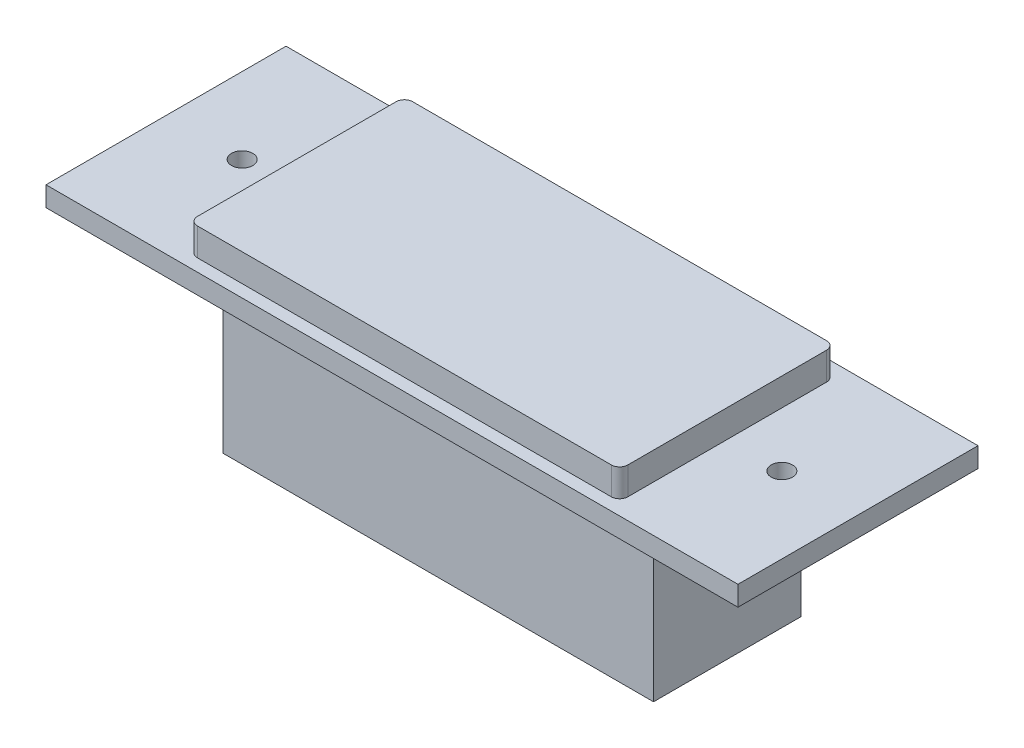
SolidWorks part; units mm, degrees
ref_plane "Front Plane" through (0, 0, 0) normal (0, 0, 1) x (1, 0, 0)
ref_plane "Top Plane" through (0, 0, 0) normal (0, 1, 0) x (1, 0, 0)
ref_plane "Right Plane" through (0, 0, 0) normal (1, 0, 0) x (0, 0, -1)
sketch "Sketch1" plane through (0, 0, 0) normal (0, 1, 0) x (1, 0, 0)
  line L1 (-33.02, 16.51) -> (33.02, 16.51)
  line L2 (-33.02, 16.51) -> (-33.02, -16.51)
  line L3 (-33.02, -16.51) -> (33.02, -16.51)
  line L4 (33.02, 16.51) -> (33.02, -16.51)
  line L5 (-33.02, 16.51) -> (33.02, -16.51) construction
  line L6 (-33.02, -16.51) -> (33.02, 16.51) construction
  point P0 (0, 0)
  dimension "D1" = 66.04
  dimension "D2" = 33.02
extrude "Boss-Extrude1" add sketch "Sketch1" along normal blind 4.2418
fillet "Fillet1" radius 1.27 4 edges at (33.02, 2.1209, 16.51) (33.02, 2.1209, -16.51) (-33.02, 2.1209, -16.51) (-33.02, 2.1209, 16.51)
sketch "Sketch2" plane through (0, 0, 0) normal (0, -1, 0) x (1, 0, 0)
  line L1 (53.086, 18.415) -> (-53.086, 18.415)
  line L2 (53.086, 18.415) -> (53.086, -18.415)
  line L3 (53.086, -18.415) -> (-53.086, -18.415)
  line L4 (-53.086, 18.415) -> (-53.086, -18.415)
  line L5 (53.086, 18.415) -> (-53.086, -18.415) construction
  line L6 (53.086, -18.415) -> (-53.086, 18.415) construction
  point P0 (0, 0)
  dimension "D1" = 36.83
  dimension "D2" = 106.172
extrude "Boss-Extrude2" add sketch "Sketch2" along normal blind 3.048
sketch "Sketch3" plane through (0, 0, 0) normal (0, 1, 0) x (1, 0, 0)
  line L0 (-53.086, 0) -> (-41.402, 0) construction
  line L1 (-53.086, -18.415) -> (-53.086, 18.415) construction
  line L2 (-41.402, 0) -> (41.402, 0) construction
  line L3 (41.402, 0) -> (53.086, 0) construction
  line L4 (53.086, 18.415) -> (53.086, -18.415) construction
  dimension "D1" = 82.804
hole_wizard "#4 Clearance Hole1" positions "Sketch4" profile "Sketch5" hole size "#4" standard "ANSI Inch" end condition through all
sketch "Sketch4" plane through (0, 0, 0) normal (0, 1, 0) x (1, 0, 0)
  point P0 (-41.402, 0)
  point P3 (41.402, 0)
sketch "Sketch5" plane through (-41.402, 0, 0) normal (1, 0, 0) x (0, 0, 1)
  line L0 (0, 0) -> (0, 3.048)
  line L1 (0, 3.048) -> (1.6319, 3.048)
  line L2 (1.6319, 3.048) -> (1.6319, 0)
  line L5 (1.6319, 0) -> (0, 0)
  line L11 (0, -6.35) -> (0, 107.95) construction
  dimension "Thru Hole Dia." = 3.2639
  dimension "Thru Hole Depth" = 3.048
sketch "Sketch6" plane through (0, -3.048, 0) normal (0, -1, 0) x (1, 0, 0)
  line L1 (33.02, 11.303) -> (-33.02, 11.303)
  line L2 (33.02, 11.303) -> (33.02, -11.303)
  line L3 (33.02, -11.303) -> (-33.02, -11.303)
  line L4 (-33.02, 11.303) -> (-33.02, -11.303)
  line L5 (33.02, 11.303) -> (-33.02, -11.303) construction
  line L6 (33.02, -11.303) -> (-33.02, 11.303) construction
  point P0 (0, 0)
  dimension "D1" = 66.04
  dimension "D2" = 22.606
extrude "Boss-Extrude3" add sketch "Sketch6" along normal blind 26.162
